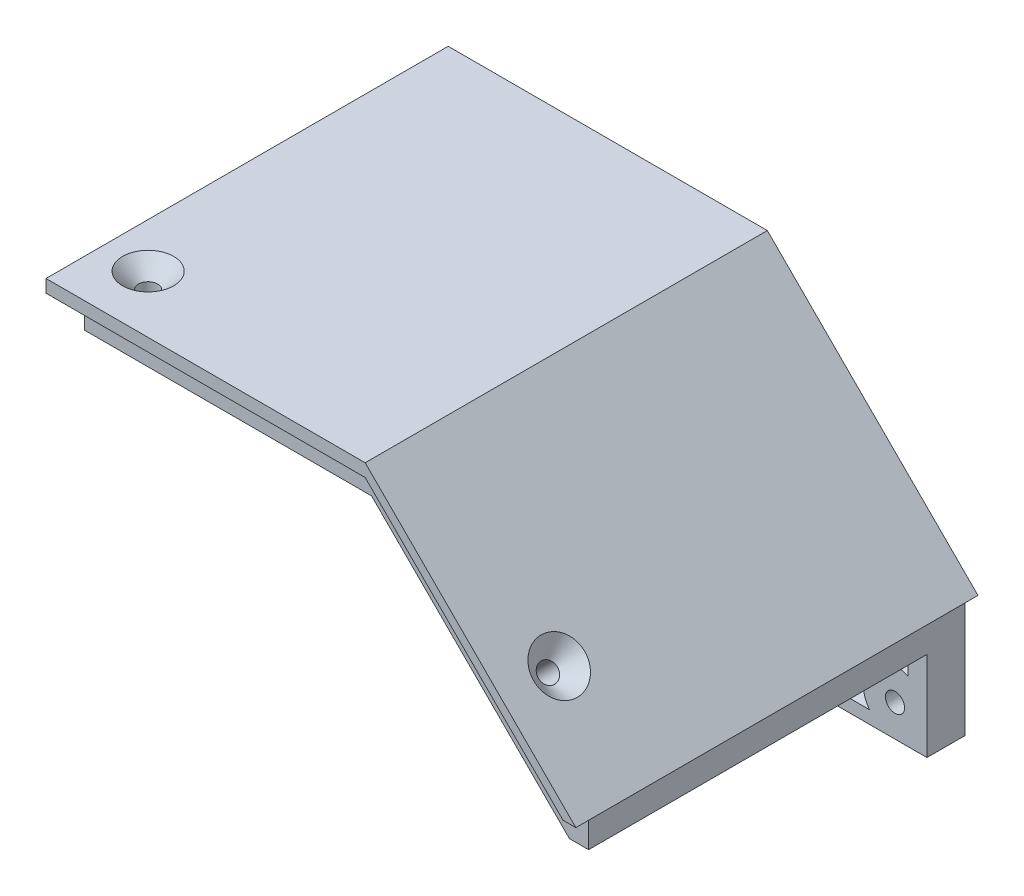
SolidWorks part; units mm, degrees
ref_plane "Спереди" through (0, 0, 0) normal (0, 0, 1) x (1, 0, 0)
ref_plane "Сверху" through (0, 0, 0) normal (0, 1, 0) x (1, 0, 0)
ref_plane "Справа" through (0, 0, 0) normal (1, 0, 0) x (0, 0, -1)
sketch "Эскиз1" plane through (0, 0, 0) normal (0, 0, 1) x (1, 0, 0)
  line L0 (0, 0) -> (-31, 31)
  line L1 (0, 0) -> (2, 0)
  line L2 (2, 0) -> (-31, 33)
  line L3 (-31, 33) -> (-81, 33)
  line L7 (-81, 31) -> (-31, 31)
  line L8 (-81, 33) -> (-81, 31)
  dimension "D1" = 31
  dimension "D2" = 45
  dimension "D3" = 2
  dimension "D4" = 2
  dimension "D5" = 83
extrude "Бобышка-Вытянуть1" add sketch "Эскиз1" along normal blind 63
sketch "Эскиз2" plane through (0, 0, 0) normal (0, 0, -1) x (-1, 0, 0)
  line L0 (0, 0) -> (31, 31)
  line L1 (31, 31) -> (79, 31)
  line L2 (0, 0) -> (0, -20)
  line L3 (81, 31) -> (31, 31) construction
  line L4 (81, 33) -> (81, 31) construction
  line L5 (79, 31) -> (79, -20)
  line L6 (79, -20) -> (0, -20)
  dimension "D1" = 2
  dimension "D2" = 20
extrude "Бобышка-Вытянуть2" add sketch "Эскиз2" against normal blind 3
sketch "Эскиз3" plane through (0, 0, 3) normal (0, 0, 1) x (1, 0, 0)
  line L0 (0, 0) -> (0, -6)
  line L1 (0, 0) -> (0, -20) construction
  line L2 (0, -6) -> (-3, -6)
  line L3 (-3, -6) -> (-3, 3)
  line L4 (-31, 31) -> (0, 0) construction
  line L5 (-3, 3) -> (0, 0)
  line L7 (-79, 31) -> (-76, 31)
  line L8 (-79, 31) -> (-79, 25)
  line L9 (-79, 25) -> (-76, 25)
  line L10 (-76, 31) -> (-76, 25)
  dimension "D1" = 6
  dimension "D2" = 3
  dimension "D3" = 6
  dimension "D4" = 3
extrude "Бобышка-Вытянуть3" add sketch "Эскиз3" along normal offset from surface (56 mm away) 4 up to face at (-37, 21.3333, 63)
sketch "Эскиз5" plane through (0, 0, 59) normal (0, 0, 1) x (1, 0, 0)
  line L0 (-79, 25) -> (-76, 25)
  line L1 (-76, 25) -> (-34, 25)
  line L2 (-34, 25) -> (-3, -6)
  line L3 (-3, -6) -> (0, -6)
  line L4 (0, -6) -> (0, 0)
  line L5 (0, 0) -> (-31, 31)
  line L6 (-31, 31) -> (-79, 31)
  line L7 (-79, 31) -> (-79, 25)
extrude "Бобышка-Вытянуть4" add sketch "Эскиз5" against normal blind 3
sketch "Эскиз6" plane through (0, 25, 0) normal (0, -1, 0) x (1, 0, 0)
  line L0 (-76, 56) -> (-76, 3) construction
  line L1 (-79, 0) -> (-76, 0)
  line L2 (-79, 0) -> (-79, 6)
  line L3 (-79, 6) -> (-76, 6)
  line L4 (-76, 0) -> (-76, 6)
  dimension "D1" = 6
extrude "Бобышка-Вытянуть5" add sketch "Эскиз6" along normal up to surface (45 mm away) up to face at (-39.5, -20, 1.5)
sketch "Эскиз7" plane through (0, -6, 0) normal (0, -1, 0) x (1, 0, 0)
  line L0 (-3, 56) -> (-3, 3) construction
  line L1 (0, 0) -> (-3, 0)
  line L2 (0, 0) -> (0, 6)
  line L3 (0, 6) -> (-3, 6)
  line L4 (-3, 0) -> (-3, 6)
  dimension "D1" = 6
extrude "Бобышка-Вытянуть6" add sketch "Эскиз7" along normal up to surface (14 mm away) up to face at (-51.6667, -20, 3)
sketch "Эскиз8" plane through (0, 0, 0) normal (0, 0, -1) x (-1, 0, 0)
  line L0 (0, -20) -> (79, -20) construction
  circle A0 centre (39.5, -20) radius 4
  dimension "D1" = 8
extrude "Вырез-Вытянуть1" cut sketch "Эскиз8" against normal blind 3
sketch "Эскиз9" plane through (0, 0, 3) normal (0, 0, 1) x (1, 0, 0)
  line L0 (-3, -20) -> (-35.5, -20) construction
  line L1 (-43.5, -20) -> (-76, -20) construction
  line L2 (-3, -20) -> (-35.5, -20)
  line L3 (-43.5, -20) -> (-76, -20)
  line L4 (-76, -20) -> (-76, -18)
  line L5 (-76, -20) -> (-76, 25) construction
  line L6 (-76, -18) -> (-45.1569, -18)
  line L7 (-3, -20) -> (-3, -18)
  line L8 (-3, -20) -> (-3, -6) construction
  line L9 (-3, -18) -> (-33.8431, -18)
  arc A0 (-35.5, -20) -> (-43.5, -20) centre (-39.5, -20) ccw construction
  arc A1 (-35.5, -20) -> (-43.5, -20) centre (-39.5, -20) ccw
  arc A2 (-45.1569, -18) -> (-33.8431, -18) centre (-39.5, -20) cw
  dimension "D2" = 6
  dimension "D1" = 2
extrude "Бобышка-Вытянуть7" add sketch "Эскиз9" along normal up to surface (3 mm away) up to face at (-77.5, 2.5, 6)
sketch "Эскиз10" plane through (0, 0, 3) normal (0, 0, 1) x (1, 0, 0)
  line L0 (-43.5, -20) -> (-79, -20) construction
  line L1 (-79, -20) -> (-79, 25) construction
  line L3 (0, -20) -> (0, -6) construction
  circle A0 centre (-74, -15) radius 5
  circle A2 centre (-5, -15) radius 5
  dimension "D1" = 10
  dimension "D6" = 10
  dimension "D2" = 5
  dimension "D3" = 5
  dimension "D7" = 5
extrude "Бобышка-Вытянуть8" add sketch "Эскиз10" along normal up to surface (3 mm away) up to face at (-39.5, -8.8333, 6)
sketch "Эскиз11" plane through (0, 0, 6) normal (0, 0, 1) x (1, 0, 0)
  line L0 (-79, -20) -> (-79, 31) construction
  circle A1 centre (-74, -15) radius 1.5
  circle A2 centre (-5, -15) radius 1.5
  dimension "D2" = 3
  dimension "D3" = 3
  dimension "D4" = 5
sketch "Эскиз12" plane through (0, 31, 0) normal (0, -1, 0) x (1, 0, 0)
  line L0 (-79, 59) -> (-79, 6) construction
  line L1 (-79, 59) -> (-31, 59) construction
  circle A0 centre (-74, 54) radius 5
  dimension "D1" = 10
  dimension "D2" = 5
  dimension "D3" = 5
extrude "Бобышка-Вытянуть9" add sketch "Эскиз12" along normal up to surface (6 mm away) up to face at (-63, 25, 40.3333)
sketch "Эскиз13" plane through (0, 25, 0) normal (0, -1, 0) x (1, 0, 0)
  circle A0 centre (-74, 54) radius 1.5
  dimension "D1" = 3
extrude "Вырез-Вытянуть3" cut sketch "Эскиз13" against normal through all both and the other way through all
chamfer "Фаска2" distance 2.5 angle 45 1 edges at (-74, 33, 52.5)
sketch "Эскиз14" plane through (0, 0, 0) normal (-0.7071, -0.7071, 0) x (0, 0, 1)
  line L0 (59, 43.8406) -> (59, 0) construction
  line L2 (63, 0) -> (59, 0) construction
  circle A0 centre (54, 15) radius 5
  dimension "D1" = 10
  dimension "D2" = 5
  dimension "D3" = 15
extrude "Бобышка-Вытянуть10" add sketch "Эскиз14" along normal up to surface (6.364 mm away) up to face at (-18.5, 9.5, 57.5)
sketch "Эскиз15" plane through (-4.5, -4.5, 0) normal (-0.7071, -0.7071, 0) x (0, 0, 1)
  circle A0 centre (54, 15) radius 1.5
  dimension "D1" = 3
extrude "Вырез-Вытянуть4" cut sketch "Эскиз15" against normal through all both and the other way through all
chamfer "Фаска3" distance 2.5 angle 45 1 edges at (-8.5459, 10.5459, 54)
extrude "Вырез-Вытянуть5" cut sketch "Эскиз11" against normal through all both and the other way through all
chamfer "Фаска4" distance 3 angle 50 5 edges at (-8.921, -11.8974, 3) (-70.079, -11.8974, 3) (-21.4216, -18, 3) (-39.5, -14, 3) (-57.5784, -18, 3) first distance on face at (-7.4605, -13.0531, 4.5) first distance on face at (-71.5395, -13.0531, 4.5) first distance on face at (-21.4216, -18, 4.5) first distance on face at (-39.5, -16, 4.5) first distance on face at (-57.5784, -18, 4.5)
